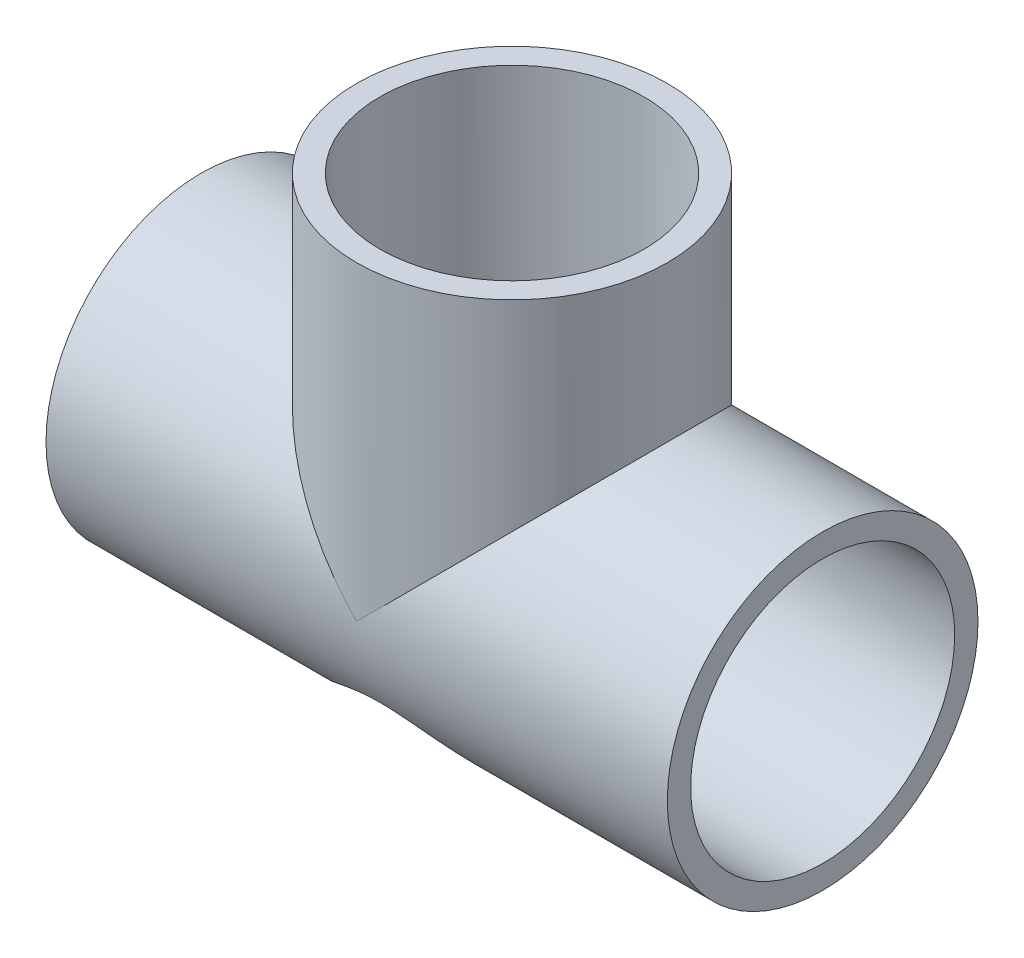
SolidWorks part; units mm, degrees
ref_plane "前视基准面" through (0, 0, 0) normal (0, 0, 1) x (1, 0, 0)
ref_plane "上视基准面" through (0, 0, 0) normal (0, 1, 0) x (1, 0, 0)
ref_plane "右视基准面" through (0, 0, 0) normal (1, 0, 0) x (0, 0, -1)
other "Configuration Table"
sketch "草图1" plane through (0, 0, 0) normal (1, 0, 0) x (0, 0, -1)
  circle A0 centre (0, 0) radius 50
  circle A1 centre (0, 0) radius 42.5
  dimension "D1" = 100
  dimension "D2" = 85
extrude "凸台-拉伸1" add sketch "草图1" along normal mid plane 100
ref_plane "基准面1" through (0, 100, 0) normal (0, 1, 0) x (1, 0, 0)
extrude "凸台-拉伸2" add sketch "草图1<2>" along normal mid plane 200
sketch "草图1<2>" plane through (0, 0, 0) normal (1, 0, 0) x (0, 0, -1) same geometry as "草图1"
sketch "草图2" plane through (0, 100, 0) normal (0, 1, 0) x (1, 0, 0)
  circle A0 centre (0, 0) radius 50
  circle A1 centre (0, 0) radius 42.5
  dimension "D1" = 100
  dimension "D2" = 85
extrude "凸台-拉伸3" add sketch "草图2" against normal up to next
sketch "草图3" plane through (0, 0, 0) normal (0, 1, 0) x (1, 0, 0)
  circle A0 centre (0, 0) radius 42.5
  dimension "D1" = 85
extrude "切除-拉伸1" cut sketch "草图3" against normal blind 200
extrude "切除-拉伸2" cut sketch "草图3<2>" against normal mid plane 200
sketch "草图3<2>" plane through (0, 0, 0) normal (0, 1, 0) x (1, 0, 0) same geometry as "草图3"
